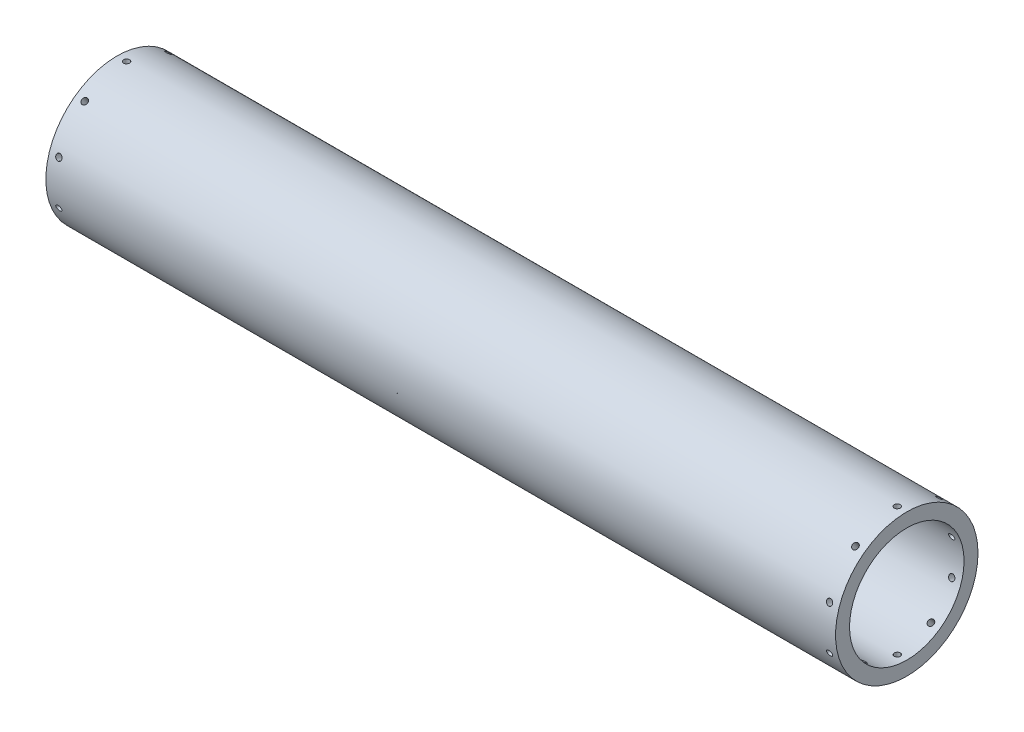
SolidWorks part; units mm, degrees
material "7075-T6 (SN)"
ref_plane "Front Plane" through (0, 0, 0) normal (0, 0, 1) x (1, 0, 0)
ref_plane "Top Plane" through (0, 0, 0) normal (0, 1, 0) x (1, 0, 0)
ref_plane "Right Plane" through (0, 0, 0) normal (1, 0, 0) x (0, 0, -1)
sketch "Sketch1" plane through (0, 0, 0) normal (1, 0, 0) x (0, 0, -1)
  circle A0 centre (0, 0) radius 45.9486
  circle A1 centre (0, 0) radius 57.15
  dimension "D1" = 91.8972
  dimension "D2" = 114.3
extrude "Boss-Extrude1" add sketch "Sketch1" along normal blind 633.73
sketch "Sketch2" plane through (0, 0, 0) normal (-1, 0, 0) x (0, 0, 1)
  circle A0 centre (0, 0) radius 44.577
  circle A1 centre (0, 0) radius 45.9486
  dimension "D1" = 89.154
extrude "Boss-Extrude2" add sketch "Sketch2" against normal blind 91.44
sketch "Sketch4" plane through (0, 0, 0) normal (0, 0, 1) x (1, 0, 0)
  line L0 (0, 0) -> (0, 88.0135) construction
  line L1 (0, 57.15) -> (0, -57.15) construction
  line L2 (0, -62.865) -> (0, 62.865) construction
ref_plane "Plane1" through (0, 57.15, 0) normal (0, 1, 0) x (1, 0, 0)
sketch "Sketch6" plane through (0, 57.15, 0) normal (0, 1, 0) x (1, 0, 0)
  line L0 (0, 57.15) -> (0, -57.15) construction
  circle A0 centre (7.62, 0) radius 2.413
  dimension "D1" = 4.826
  dimension "D2" = 7.62
extrude "Cut-Extrude1" cut sketch "Sketch6" against normal blind 15.24
pattern_circular "CirPattern1" count 10 every 36 about axis through (0, 0, 0) along (-1, 0, 0) of "Cut-Extrude1"
sketch "Sketch7" plane through (0, 57.15, 0) normal (0, 1, 0) x (1, 0, 0)
  line L0 (633.73, -57.15) -> (633.73, 57.15) construction
  circle A0 centre (626.11, 0) radius 2.413
  dimension "D2" = 4.826
  dimension "D1" = 7.62
extrude "Cut-Extrude2" cut sketch "Sketch7" against normal blind 15.24
pattern_circular "CirPattern2" count 10 every 36 about axis through (633.73, 0, 0) along (1, 0, 0) of "Cut-Extrude2"
